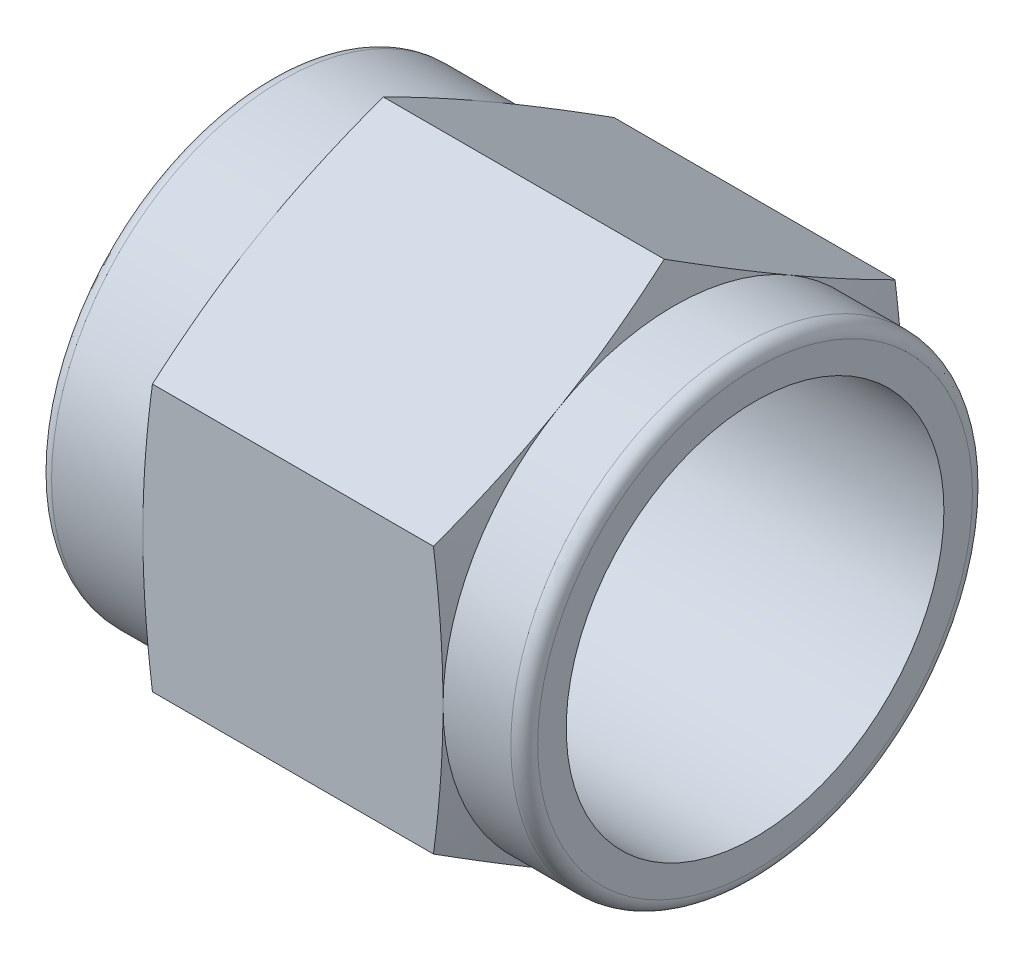
SolidWorks part; units mm, degrees
material "6061-T6 (SS)"
ref_plane "Front Plane" through (0, 0, 0) normal (0, 0, 1) x (1, 0, 0)
ref_plane "Top Plane" through (0, 0, 0) normal (0, 1, 0) x (1, 0, 0)
ref_plane "Right Plane" through (0, 0, 0) normal (1, 0, 0) x (0, 0, -1)
sketch "Sketch1" plane through (0, 0, 0) normal (0, 0, 1) x (1, 0, 0)
  line L0 (9.1948, 0) -> (-9.1948, 0) construction
  point P2 (6.1214, 0)
  point P3 (-5.2324, 0)
  point P5 (-5.2578, 0)
  dimension "M" = 18.3896
  dimension "L" = 15.3162
  dimension "B" = 3.9624
  dimension "S" = 14.4526
sketch "Sketch2" plane through (0, 0, 0) normal (1, 0, 0) x (0, 0, -1)
  line L1 (0, 10.082) -> (-8.7312, 5.041)
  line L2 (-8.7312, 5.041) -> (-8.7312, -5.041)
  line L3 (-8.7312, -5.041) -> (0, -10.082)
  line L4 (0, -10.082) -> (8.7312, -5.041)
  line L5 (8.7312, -5.041) -> (8.7312, 5.041)
  line L6 (8.7312, 5.041) -> (0, 10.082)
  circle A0 centre (0, 0) radius 8.7312 construction
  circle A1 centre (0, 0) radius 4.7625 construction
  circle A2 centre (0, 0) radius 5.588
  dimension "Hex" = 17.4625
  dimension "Tube OD" = 9.525
  dimension "A" = 11.176
sketch "Sketch3" plane through (0, 0, 0) normal (1, 0, 0) x (0, 0, -1)
  line L0 (8.7312, 5.041) -> (0, 10.082) construction
  line L1 (8.7312, -5.041) -> (8.7312, 5.041) construction
  line L2 (0, -10.082) -> (8.7312, -5.041) construction
  line L3 (-8.7312, -5.041) -> (0, -10.082) construction
  line L4 (-8.7312, 5.041) -> (-8.7312, -5.041) construction
  line L5 (0, 10.082) -> (-8.7312, 5.041) construction
  line L6 (8.7312, 5.041) -> (0, 10.082)
  line L7 (8.7312, -5.041) -> (8.7312, 5.041)
  line L8 (0, -10.082) -> (8.7312, -5.041)
  line L9 (-8.7312, -5.041) -> (0, -10.082)
  line L10 (-8.7312, 5.041) -> (-8.7312, -5.041)
  line L11 (0, 10.082) -> (-8.7312, 5.041)
  circle A1 centre (0, 0) radius 5.588 construction
  circle A2 centre (0, 0) radius 5.588
extrude "Boss-Extrude1" add sketch "Sketch3" against normal up to vertex (9.1948 mm away) and the other way up to vertex (9.1948 mm away) up to point (-9.1948, 0, 0) other way up to point (9.1948, 0, 0)
sketch "Sketch4" plane through (-9.1948, 0, 0) normal (-1, 0, 0) x (0, 0, 1)
  circle A0 centre (0, 0) radius 8.7312 construction
  circle A1 centre (0, 0) radius 8.7312
extrude "Cut-Extrude1" cut sketch "Sketch4" against normal up to vertex (3.9624 mm away) flip side to cut up to point (-5.2324, 0, 0)
sketch "Sketch5" plane through (9.1948, 0, 0) normal (1, 0, 0) x (0, 0, -1)
  circle A0 centre (0, 0) radius 8.7312 construction
  circle A1 centre (0, 0) radius 8.7312
extrude "Cut-Extrude2" cut sketch "Sketch5" against normal up to vertex (3.0734 mm away) flip side to cut up to point (6.1214, 0, 0)
sketch "Sketch6" plane through (-5.2324, 0, 0) normal (-1, 0, 0) x (0, 0, 1)
  circle A1 centre (0, 0) radius 8.7312
  circle A2 centre (0, 0) radius 8.7312
  dimension "D1" = 0
extrude "Cut-Extrude3" cut sketch "Sketch6" against normal through all draft 75 flip side to cut
sketch "Sketch7" plane through (6.1214, 0, 0) normal (1, 0, 0) x (0, 0, -1)
  circle A1 centre (0, 0) radius 8.7312
  circle A2 centre (0, 0) radius 8.7312
  dimension "D1" = 0
extrude "Cut-Extrude4" cut sketch "Sketch7" against normal through all draft 75 flip side to cut
sketch "Sketch8" plane through (9.1948, 0, 0) normal (1, 0, 0) x (0, 0, -1)
  circle A0 centre (0, 0) radius 7.1438
  dimension "Thread OD" = 14.2875
extrude "Cut-Extrude5" cut sketch "Sketch8" against normal up to vertex (14.4272 mm away) up to point (-5.2324, 0, 0)
chamfer "Chamfer1" distance 0.381 angle 45 2 edges at (-5.2324, 0, -5.588) (-9.1948, 0, -5.588)
fillet "Fillet1" radius 0.508 2 edges at (9.1948, 0, -8.7312) (-9.1948, 0, -8.7312)
ref_plane "Plane1" through (-5.2578, 0, 0) normal (1, 0, 0) x (0, 0, -1)
sketch "Sketch9" plane through (-5.2578, 0, 0) normal (1, 0, 0) x (0, 0, -1)
  circle A0 centre (0, 0) radius 7.1438 construction
  circle A1 centre (0, 0) radius 7.1438
curve "Helix/Spiral1" [suppressed] pitch 1.4111 height 15.8637 turns 11.242 parameters "Pitch"=1.4111
sketch "Sketch11" plane through (0, 0, 0) normal (0, 0, 1) x (1, 0, 0)
  line L0 (9.1948, 7.1437) -> (7.5015, 7.1437)
  line L1 (7.5015, 7.1437) -> (0.3577, 0)
  line L2 (0.3577, 0) -> (9.1948, 0)
  line L3 (9.1948, 0) -> (9.1948, 7.1437)
  line L4 (9.1948, -7.1438) -> (9.1948, 7.1437) construction
  dimension "D1" = 1.6933
  dimension "D2" = 45
sketch "Sketch10" plane through (0, 0, 0) normal (0, 0, 1) x (1, 0, 0)
  line L0 (-5.8752, 7.1437) -> (-4.6404, 7.1437)
  line L1 (-5.8752, 7.1437) -> (-5.346, 6.2272)
  line L2 (-5.346, 6.2272) -> (-5.1696, 6.2272)
  line L3 (-5.1696, 6.2272) -> (-4.6404, 7.1437)
  line L4 (-5.2578, 6.2272) -> (-5.2578, 7.1437) construction
  line L5 (-5.6106, 6.6855) -> (-4.905, 6.6855) construction
  dimension "D1" = 60
  dimension "D2" = 0.1764
  dimension "D3" = 0.7056
sweep "Sweep1" [suppressed] add profiles "Sketch10" path "Helix/Spiral1"
revolve "Cut-Revolve1" [suppressed] cut sketch "Sketch11" angle 360 about L0
equation "\"D3@Helix/Spiral1\" = \"S@Sketch1\"+\"Pitch@Helix/Spiral1\""
equation "\"D2@Sketch10\" = \"Pitch@Helix/Spiral1\"*.125"
equation "\"D3@Sketch10\" = \"Pitch@Helix/Spiral1\"*.50"
equation "\"D1@Sketch11\" = \"Pitch@Helix/Spiral1\"*1.2"
